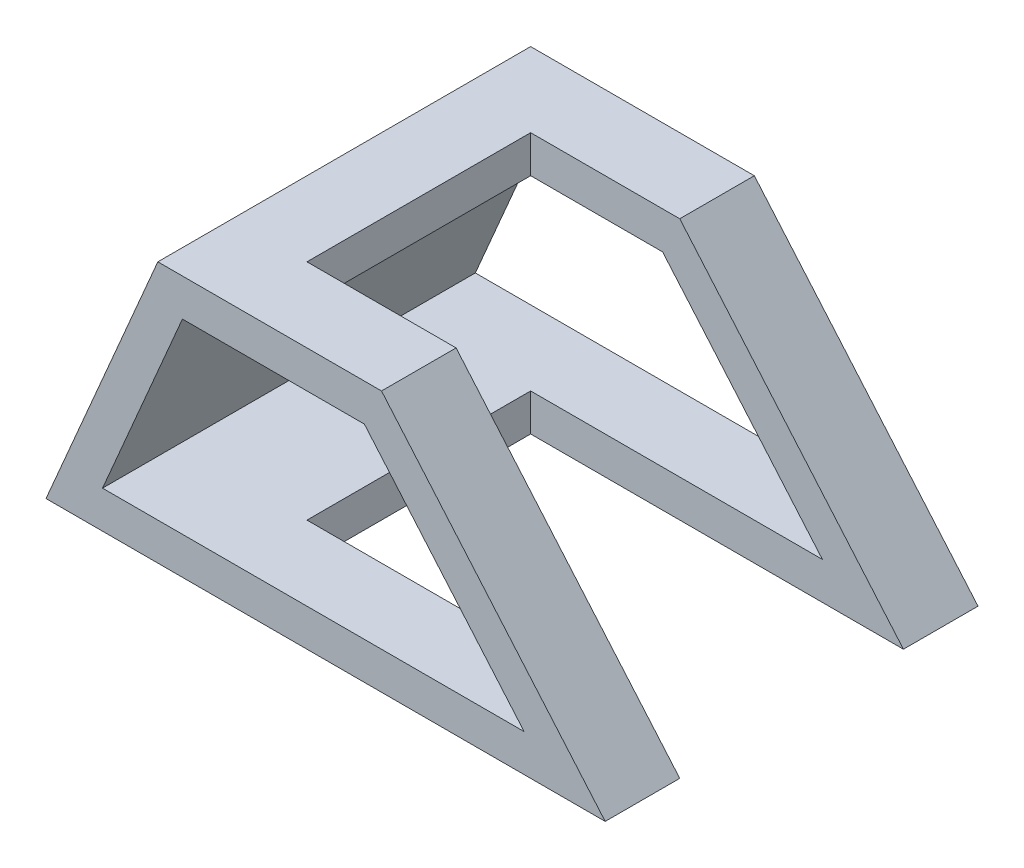
SolidWorks part; units mm, degrees
material "AISI 1020"
ref_plane "Plan de face" through (0, 0, 0) normal (0, 0, 1) x (1, 0, 0)
ref_plane "Plan de dessus" through (0, 0, 0) normal (0, 1, 0) x (1, 0, 0)
ref_plane "Plan de droite" through (0, 0, 0) normal (1, 0, 0) x (0, 0, -1)
sketch "Esquisse1" plane through (0, 0, 0) normal (0, 0, 1) x (1, 0, 0)
  line L0 (0, 0) -> (30, 70)
  line L1 (30, 70) -> (90, 70)
  line L2 (90, 70) -> (150, 0)
  line L3 (150, 0) -> (0, 0)
  line L4 (36.594, 60) -> (85.4007, 60)
  line L5 (85.4007, 60) -> (128.2578, 10)
  line L6 (128.2578, 10) -> (15.1654, 10)
  line L7 (15.1654, 10) -> (36.594, 60)
  dimension "D1" = 70
  dimension "D2" = 30
  dimension "D3" = 60
  dimension "D4" = 150
  dimension "D5" = 10
extrude "Boss.-Extru.1" add sketch "Esquisse1" along normal blind 100
sketch "Esquisse2" plane through (0, 70, 0) normal (0, 1, 0) x (1, 0, 0)
  line L0 (90, -100) -> (90, 0) construction
  line L1 (50, -20) -> (150, -20)
  line L2 (50, -20) -> (50, -80)
  line L3 (50, -80) -> (150, -80)
  line L4 (150, -20) -> (150, -80)
  line L6 (30, 0) -> (0, 0) construction
  dimension "D1" = 40
  dimension "D2" = 100
  dimension "D3" = 20
  dimension "D4" = 60
extrude "Enlèv. mat.-Extru.1" cut sketch "Esquisse2" against normal blind 171
